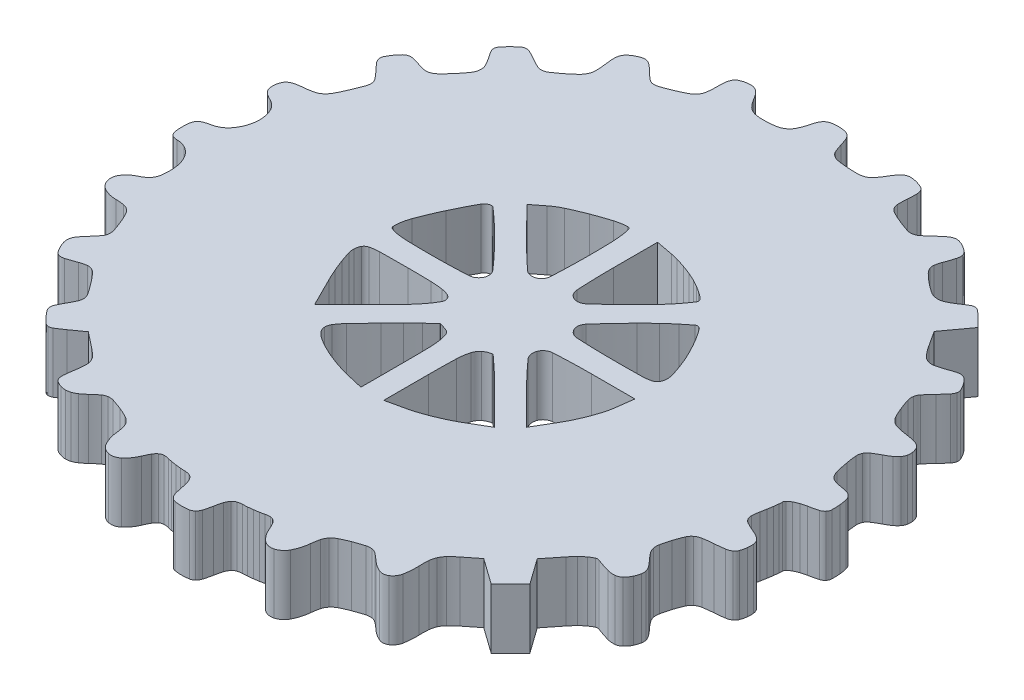
SolidWorks part; units mm, degrees
ref_plane "Front Plane" through (0, 0, 0) normal (0, 0, 1) x (1, 0, 0)
ref_plane "Top Plane" through (0, 0, 0) normal (0, 1, 0) x (1, 0, 0)
ref_plane "Right Plane" through (0, 0, 0) normal (1, 0, 0) x (0, 0, -1)
sketch "Sketch1" plane through (0, 0, 0) normal (0, 1, 0) x (1, 0, 0)
  line L204 (10740.0744, 3244.2085) -> (10740.2834, 3244.3574)
  line L205 (10740.2834, 3244.3574) -> (10740.527, 3244.1668)
  line L206 (10746.6423, 3244.2023) -> (10746.8657, 3244.3792)
  line L207 (10746.8657, 3244.3792) -> (10747.0818, 3244.2253)
  line L208 (10747.0818, 3244.2253) -> (10747.2978, 3244.0715)
  line L209 (10747.2978, 3244.0715) -> (10747.4591, 3244.2328)
  line L210 (10747.4591, 3244.2328) -> (10747.6204, 3244.3941)
  line L211 (10747.6204, 3244.3941) -> (10747.4678, 3244.6085)
  line L212 (10747.4678, 3244.6085) -> (10747.3151, 3244.8229)
  line L213 (10747.3151, 3244.8229) -> (10747.5289, 3245.0914)
  line L214 (10747.5042, 3251.1741) -> (10747.3419, 3251.4249)
  line L215 (10747.3419, 3251.4249) -> (10747.496, 3251.6365)
  line L216 (10747.496, 3251.6365) -> (10747.6501, 3251.8481)
  line L217 (10747.6501, 3251.8481) -> (10747.4943, 3252.0039)
  line L218 (10742.5971, 3249.3628) -> (10742.104, 3249.8615)
  line L219 (10742.104, 3249.8615) -> (10742.2945, 3250.0106)
  line L220 (10743.7423, 3249.6702) -> (10743.7423, 3250.405)
  line L221 (10743.7423, 3250.405) -> (10744.0245, 3250.3521)
  line L222 (10742.3156, 3247.1719) -> (10741.7813, 3246.6376)
  line L223 (10741.7813, 3246.6376) -> (10741.5426, 3247.1153)
  line L224 (10745.5314, 3246.9876) -> (10745.3248, 3246.6351)
  line L225 (10745.3248, 3246.6351) -> (10744.7969, 3247.163)
  line L226 (10745.094, 3247.9496) -> (10745.8197, 3247.9496)
  line L227 (10745.8197, 3247.9496) -> (10745.7789, 3247.6449)
  line L228 (10743.3613, 3246.5779) -> (10743.3613, 3245.8321)
  line L229 (10743.3613, 3245.8321) -> (10743.1136, 3245.8895)
  line L230 (10742.9516, 3247.272) -> (10743.0949, 3247.412)
  line L231 (10744.5341, 3246.8912) -> (10745.0551, 3246.3661)
  line L232 (10745.0551, 3246.3661) -> (10744.7226, 3246.1716)
  line L233 (10744.0661, 3245.9047) -> (10743.7423, 3245.8322)
  line L234 (10743.7423, 3245.8322) -> (10743.7423, 3246.5798)
  arc A2462 (10743.2549, 3253.2157) -> (10743.3129, 3253.3789) centre (10742.4844, 3253.5816) ccw
  arc A2463 (10743.1745, 3253.1207) -> (10743.2549, 3253.2157) centre (10743.0352, 3253.3201) ccw
  arc A2464 (10743.0513, 3253.0716) -> (10743.1745, 3253.1207) centre (10743.0082, 3253.3586) ccw
  arc A2465 (10742.8512, 3253.0562) -> (10743.0513, 3253.0716) centre (10742.8445, 3254.4507) ccw
  arc A2466 (10742.726, 3253.0669) -> (10742.8512, 3253.0562) centre (10742.8479, 3253.7578) ccw
  arc A2467 (10742.6323, 3253.101) -> (10742.726, 3253.0669) centre (10742.7756, 3253.3483) ccw
  arc A2468 (10742.555, 3253.1659) -> (10742.6323, 3253.101) centre (10742.7801, 3253.3559) ccw
  arc A2469 (10742.4801, 3253.2713) -> (10742.555, 3253.1659) centre (10743.1453, 3253.6642) ccw
  arc A2470 (10742.4801, 3253.2713) -> (10742.4087, 3253.375) centre (10741.7003, 3252.8107) ccw
  arc A2471 (10742.4087, 3253.375) -> (10742.3409, 3253.4339) centre (10742.2162, 3253.2217) ccw
  arc A2472 (10742.3409, 3253.4339) -> (10742.2652, 3253.4579) centre (10742.2502, 3253.2796) ccw
  arc A2473 (10742.2652, 3253.4579) -> (10742.171, 3253.4529) centre (10742.2362, 3253.1121) ccw
  arc A2474 (10742.171, 3253.4529) -> (10742.0772, 3253.4222) centre (10742.2438, 3253.0722) ccw
  arc A2475 (10742.0772, 3253.4222) -> (10742.0235, 3253.3729) centre (10742.1304, 3253.3104) ccw
  arc A2476 (10742.0235, 3253.3729) -> (10741.9965, 3253.29) centre (10742.2002, 3253.2696) ccw
  arc A2477 (10741.9965, 3253.29) -> (10741.9889, 3253.1414) centre (10743.5182, 3253.1371) ccw
  arc A2478 (10741.9777, 3252.9816) -> (10741.9889, 3253.1414) centre (10740.7895, 3253.1448) ccw
  arc A2479 (10741.9402, 3252.8893) -> (10741.9777, 3252.9816) centre (10741.7784, 3253.009) ccw
  arc A2480 (10741.8602, 3252.8203) -> (10741.9402, 3252.8893) centre (10741.7469, 3253.0323) ccw
  arc A2481 (10741.6923, 3252.7403) -> (10741.8602, 3252.8203) centre (10740.9214, 3254.5765) ccw
  arc A2482 (10741.5022, 3252.667) -> (10741.6923, 3252.7403) centre (10740.3306, 3255.9839) ccw
  arc A2483 (10741.4105, 3252.6574) -> (10741.5022, 3252.667) centre (10741.4366, 3252.8527) ccw
  arc A2484 (10741.3315, 3252.692) -> (10741.4105, 3252.6574) centre (10741.4312, 3252.8121) ccw
  arc A2485 (10741.2073, 3252.8053) -> (10741.3315, 3252.692) centre (10742.489, 3254.087) ccw
  arc A2486 (10741.2073, 3252.8053) -> (10741.0993, 3252.9034) centre (10740.1198, 3251.7178) ccw
  arc A2487 (10741.0993, 3252.9034) -> (10741.023, 3252.9438) centre (10740.9635, 3252.739) ccw
  arc A2488 (10741.023, 3252.9438) -> (10740.9492, 3252.9445) centre (10740.9848, 3252.8124) ccw
  arc A2489 (10740.9492, 3252.9445) -> (10740.8558, 3252.9075) centre (10741.0639, 3252.5186) ccw
  arc A2490 (10740.8558, 3252.9075) -> (10740.7745, 3252.8496) centre (10741.0402, 3252.5628) ccw
  arc A2491 (10740.7745, 3252.8496) -> (10740.7318, 3252.7833) centre (10740.8826, 3252.7329) ccw
  arc A2492 (10740.7318, 3252.7833) -> (10740.7186, 3252.69) centre (10740.9779, 3252.7011) ccw
  arc A2493 (10740.7186, 3252.69) -> (10740.7324, 3252.5378) centre (10742.343, 3252.7597) ccw
  arc A2494 (10740.7446, 3252.3753) -> (10740.7324, 3252.5378) centre (10739.4289, 3252.3582) ccw
  arc A2495 (10740.724, 3252.2714) -> (10740.7446, 3252.3753) centre (10740.4889, 3252.372) ccw
  arc A2496 (10740.6625, 3252.1822) -> (10740.724, 3252.2714) centre (10740.4725, 3252.379) ccw
  arc A2497 (10740.5318, 3252.069) -> (10740.6625, 3252.1822) centre (10739.5471, 3253.3376) ccw
  arc A2498 (10740.3771, 3251.9566) -> (10740.5318, 3252.069) centre (10738.6887, 3254.4435) ccw
  arc A2499 (10740.2935, 3251.9257) -> (10740.3771, 3251.9566) centre (10740.2726, 3252.1107) ccw
  arc A2500 (10740.2096, 3251.9392) -> (10740.2935, 3251.9257) centre (10740.2757, 3252.0826) ccw
  arc A2501 (10740.0612, 3252.0158) -> (10740.2096, 3251.9392) centre (10740.9982, 3253.6485) ccw
  arc A2502 (10740.0612, 3252.0158) -> (10739.9152, 3252.0937) centre (10738.7372, 3249.7089) ccw
  arc A2503 (10739.9152, 3252.0937) -> (10739.8415, 3252.1092) centre (10739.848, 3251.9577) ccw
  arc A2504 (10739.8415, 3252.1092) -> (10739.7773, 3252.0853) centre (10739.8462, 3251.9985) ccw
  arc A2505 (10739.7773, 3252.0853) -> (10739.6811, 3251.9996) centre (10740.4764, 3251.2043) ccw
  arc A2506 (10739.6811, 3251.9996) -> (10739.5969, 3251.9063) centre (10740.5595, 3251.1212) ccw
  arc A2507 (10739.5969, 3251.9063) -> (10739.5729, 3251.8465) centre (10739.6803, 3251.8382) ccw
  arc A2508 (10739.5729, 3251.8465) -> (10739.5871, 3251.783) centre (10739.684, 3251.838) ccw
  arc A2509 (10739.5871, 3251.783) -> (10739.656, 3251.6739) centre (10740.7691, 3252.4535) ccw
  arc A2510 (10739.748, 3251.5183) -> (10739.656, 3251.6739) centre (10738.6958, 3251.0013) ccw
  arc A2511 (10739.7662, 3251.4084) -> (10739.748, 3251.5183) centre (10739.5748, 3251.4332) ccw
  arc A2512 (10739.7218, 3251.2961) -> (10739.7662, 3251.4084) centre (10739.5221, 3251.44) ccw
  arc A2513 (10739.5848, 3251.1243) -> (10739.7218, 3251.2961) centre (10737.8807, 3252.6231) ccw
  arc A2514 (10739.4699, 3251.0052) -> (10739.5848, 3251.1243) centre (10738.2475, 3252.3005) ccw
  arc A2515 (10739.3888, 3250.9568) -> (10739.4699, 3251.0052) centre (10739.3202, 3251.1639) ccw
  arc A2516 (10739.3015, 3250.9511) -> (10739.3888, 3250.9568) centre (10739.3341, 3251.1218) ccw
  arc A2517 (10739.1694, 3250.9865) -> (10739.3015, 3250.9511) centre (10739.4769, 3251.8688) ccw
  arc A2518 (10739.1694, 3250.9865) -> (10739.0422, 3251.0231) centre (10738.776, 3249.8581) ccw
  arc A2519 (10739.0422, 3251.0231) -> (10738.9637, 3251.0223) centre (10739.0046, 3250.8588) ccw
  arc A2520 (10738.9637, 3251.0223) -> (10738.9004, 3250.9862) centre (10738.9966, 3250.8909) ccw
  arc A2521 (10738.9004, 3250.9862) -> (10738.8294, 3250.9013) centre (10739.3647, 3250.5263) ccw
  arc A2522 (10738.8294, 3250.9013) -> (10738.7704, 3250.8009) centre (10739.4297, 3250.4809) ccw
  arc A2523 (10738.7704, 3250.8009) -> (10738.7619, 3250.7322) centre (10738.8669, 3250.754) ccw
  arc A2524 (10738.7619, 3250.7322) -> (10738.7963, 3250.6607) centre (10738.9227, 3250.7656) ccw
  arc A2525 (10738.7963, 3250.6607) -> (10738.9049, 3250.5391) centre (10740.5663, 3252.1308) ccw
  arc A2526 (10739.0208, 3250.4069) -> (10738.9049, 3250.5391) centre (10737.4597, 3249.1545) ccw
  arc A2527 (10739.0544, 3250.3259) -> (10739.0208, 3250.4069) centre (10738.8987, 3250.3089) ccw
  arc A2528 (10739.0429, 3250.2317) -> (10739.0544, 3250.3259) centre (10738.8479, 3250.3033) ccw
  arc A2529 (10738.9612, 3250.0252) -> (10739.0429, 3250.2317) centre (10734.8211, 3251.7819) ccw
  arc A2530 (10738.8777, 3249.8511) -> (10738.9612, 3250.0252) centre (10737.0261, 3250.8463) ccw
  arc A2531 (10738.8043, 3249.7606) -> (10738.8777, 3249.8511) centre (10738.6034, 3249.9985) ccw
  arc A2532 (10738.7102, 3249.7122) -> (10738.8043, 3249.7606) centre (10738.6521, 3249.9408) ccw
  arc A2533 (10738.5607, 3249.687) -> (10738.7102, 3249.7122) centre (10738.4814, 3250.6127) ccw
  arc A2534 (10738.5607, 3249.687) -> (10738.4253, 3249.6676) centre (10738.6636, 3248.4846) ccw
  arc A2535 (10738.4253, 3249.6676) -> (10738.3437, 3249.6338) centre (10738.4705, 3249.4431) ccw
  arc A2536 (10738.3437, 3249.6338) -> (10738.2956, 3249.5785) centre (10738.4206, 3249.5183) ccw
  arc A2537 (10738.2956, 3249.5785) -> (10738.2697, 3249.4934) centre (10738.5567, 3249.4527) ccw
  arc A2538 (10738.2697, 3249.4934) -> (10738.2701, 3249.4097) centre (10738.5552, 3249.4529) ccw
  arc A2539 (10738.2701, 3249.4097) -> (10738.2963, 3249.3415) centre (10738.4381, 3249.4351) ccw
  arc A2540 (10738.2963, 3249.3415) -> (10738.3519, 3249.2845) centre (10738.4731, 3249.4582) ccw
  arc A2541 (10738.3519, 3249.2845) -> (10738.4412, 3249.2335) centre (10738.6761, 3249.7491) ccw
  arc A2542 (10738.6102, 3249.0567) -> (10738.4412, 3249.2335) centre (10738.3046, 3248.9338) ccw
  arc A2543 (10738.6451, 3248.7765) -> (10738.6102, 3249.0567) centre (10738.0978, 3248.8506) ccw
  arc A2544 (10738.5367, 3248.5121) -> (10738.6451, 3248.7765) centre (10738.0822, 3248.8527) ccw
  arc A2545 (10738.3253, 3248.3788) -> (10738.5367, 3248.5121) centre (10738.2567, 3248.722) ccw
  arc A2546 (10738.3253, 3248.3788) -> (10738.2081, 3248.3456) centre (10738.4781, 3247.615) ccw
  arc A2547 (10738.2081, 3248.3456) -> (10738.1445, 3248.3) centre (10738.2591, 3248.2075) ccw
  arc A2548 (10738.1445, 3248.3) -> (10738.1128, 3248.2278) centre (10738.2619, 3248.2053) ccw
  arc A2549 (10738.1128, 3248.2278) -> (10738.1035, 3248.1039) centre (10738.9338, 3248.1039) ccw
  arc A2550 (10738.1035, 3248.1039) -> (10738.1104, 3247.9899) centre (10739.0429, 3248.1039) ccw
  arc A2551 (10738.1104, 3247.9899) -> (10738.1347, 3247.9224) centre (10738.2715, 3248.0096) ccw
  arc A2552 (10738.1347, 3247.9224) -> (10738.1797, 3247.8861) centre (10738.211, 3247.9711) ccw
  arc A2553 (10738.1797, 3247.8861) -> (10738.2504, 3247.8734) centre (10738.2504, 3248.0777) ccw
  arc A2554 (10738.4031, 3247.8361) -> (10738.2504, 3247.8734) centre (10738.2504, 3247.5425) ccw
  arc A2555 (10738.5278, 3247.7316) -> (10738.4031, 3247.8361) centre (10738.2294, 3247.5021) ccw
  arc A2556 (10738.6091, 3247.5702) -> (10738.5278, 3247.7316) centre (10738.147, 3247.4387) ccw
  arc A2557 (10738.6369, 3247.3711) -> (10738.6091, 3247.5702) centre (10737.9092, 3247.3711) ccw
  arc A2558 (10738.6277, 3247.2357) -> (10738.6369, 3247.3711) centre (10737.6336, 3247.3711) ccw
  arc A2559 (10738.5977, 3247.1444) -> (10738.6277, 3247.2357) centre (10738.3642, 3247.2715) ccw
  arc A2560 (10738.5404, 3247.0776) -> (10738.5977, 3247.1444) centre (10738.4131, 3247.2449) ccw
  arc A2561 (10738.4464, 3247.0214) -> (10738.5404, 3247.0776) centre (10738.2422, 3247.4695) ccw
  arc A2562 (10738.4464, 3247.0214) -> (10738.2839, 3246.8828) centre (10738.6074, 3246.668) ccw
  arc A2563 (10738.2839, 3246.8828) -> (10738.2569, 3246.7049) centre (10738.4615, 3246.7649) ccw
  arc A2564 (10738.2569, 3246.7049) -> (10738.3772, 3246.5572) centre (10738.4927, 3246.774) ccw
  arc A2565 (10738.3772, 3246.5572) -> (10738.5988, 3246.5018) centre (10738.5988, 3246.9732) ccw
  arc A2566 (10738.739, 3246.4903) -> (10738.5988, 3246.5018) centre (10738.5988, 3245.6428) ccw
  arc A2567 (10738.8258, 3246.4522) -> (10738.739, 3246.4903) centre (10738.7077, 3246.301) ccw
  arc A2568 (10738.8919, 3246.3732) -> (10738.8258, 3246.4522) centre (10738.6748, 3246.2589) ccw
  arc A2569 (10738.9648, 3246.2161) -> (10738.8919, 3246.3732) centre (10737.3608, 3245.5668) ccw
  arc A2570 (10739.0302, 3246.0376) -> (10738.9648, 3246.2161) centre (10736.329, 3245.1492) ccw
  arc A2571 (10739.0393, 3245.9438) -> (10739.0302, 3246.0376) centre (10738.8261, 3245.9705) ccw
  arc A2572 (10739.0064, 3245.862) -> (10739.0393, 3245.9438) centre (10738.8676, 3245.9653) ccw
  arc A2573 (10738.9053, 3245.7398) -> (10739.0064, 3245.862) centre (10737.7813, 3246.7735) ccw
  arc A2574 (10738.9053, 3245.7398) -> (10738.8178, 3245.6335) centre (10739.828, 3244.8912) ccw
  arc A2575 (10738.8178, 3245.6335) -> (10738.7793, 3245.553) centre (10739.0107, 3245.4917) ccw
  arc A2576 (10738.7793, 3245.553) -> (10738.7773, 3245.4744) centre (10738.9432, 3245.5096) ccw
  arc A2577 (10738.7773, 3245.4744) -> (10738.8094, 3245.3779) centre (10739.2221, 3245.5688) ccw
  arc A2578 (10738.8094, 3245.3779) -> (10738.8751, 3245.2613) centre (10739.5736, 3245.7315) ccw
  arc A2579 (10738.8751, 3245.2613) -> (10738.9372, 3245.2177) centre (10738.9628, 3245.3203) ccw
  arc A2580 (10738.9372, 3245.2177) -> (10739.0245, 3245.2198) centre (10738.977, 3245.3774) ccw
  arc A2581 (10739.0245, 3245.2198) -> (10739.2015, 3245.28) centre (10738.2661, 3247.7404) ccw
  arc A2582 (10739.3152, 3245.3089) -> (10739.2015, 3245.28) centre (10739.3843, 3244.7992) ccw
  arc A2583 (10739.3975, 3245.2954) -> (10739.3152, 3245.3089) centre (10739.3343, 3245.168) ccw
  arc A2584 (10739.479, 3245.2327) -> (10739.3975, 3245.2954) centre (10739.2801, 3245.0587) ccw
  arc A2585 (10739.603, 3245.081) -> (10739.479, 3245.2327) centre (10737.2943, 3243.32) ccw
  arc A2586 (10739.7276, 3244.9081) -> (10739.603, 3245.081) centre (10736.4902, 3242.7068) ccw
  arc A2587 (10739.7647, 3244.8166) -> (10739.7276, 3244.9081) centre (10739.5333, 3244.776) ccw
  arc A2588 (10739.7551, 3244.7302) -> (10739.7647, 3244.8166) centre (10739.612, 3244.7898) ccw
  arc A2589 (10739.6884, 3244.5948) -> (10739.7551, 3244.7302) centre (10738.65, 3245.1908) ccw
  arc A2590 (10739.6884, 3244.5948) -> (10739.6199, 3244.4632) centre (10741.2543, 3243.6962) ccw
  arc A2591 (10739.6199, 3244.4632) -> (10739.6062, 3244.3891) centre (10739.7546, 3244.3999) ccw
  arc A2592 (10739.6062, 3244.3891) -> (10739.6313, 3244.3217) centre (10739.7343, 3244.3984) ccw
  arc A2593 (10739.6313, 3244.3217) -> (10739.7157, 3244.2205) centre (10740.5942, 3245.039) ccw
  arc A2594 (10739.7157, 3244.2205) -> (10739.8153, 3244.1222) centre (10740.9298, 3245.3516) ccw
  arc A2595 (10739.8153, 3244.1222) -> (10739.8729, 3244.0989) centre (10739.8759, 3244.189) ccw
  arc A2596 (10739.8729, 3244.0989) -> (10739.9368, 3244.1162) centre (10739.8767, 3244.2114) ccw
  arc A2597 (10739.9368, 3244.1162) -> (10740.0744, 3244.2085) centre (10738.3427, 3246.6405) ccw
  arc A2598 (10740.663, 3244.0489) -> (10740.527, 3244.1668) centre (10739.4205, 3242.7529) ccw
  arc A2599 (10740.7235, 3243.9598) -> (10740.663, 3244.0489) centre (10740.4837, 3243.8618) ccw
  arc A2600 (10740.7415, 3243.8556) -> (10740.7235, 3243.9598) centre (10740.4963, 3243.867) ccw
  arc A2601 (10740.7239, 3243.6847) -> (10740.7415, 3243.8556) centre (10739.2106, 3243.9267) ccw
  arc A2602 (10740.7239, 3243.6847) -> (10740.7036, 3243.52) centre (10743.0174, 3243.318) ccw
  arc A2603 (10740.7036, 3243.52) -> (10740.7143, 3243.4345) centre (10740.9074, 3243.5022) ccw
  arc A2604 (10740.7143, 3243.4345) -> (10740.7569, 3243.381) centre (10740.8124, 3243.4689) ccw
  arc A2605 (10740.7569, 3243.381) -> (10740.8447, 3243.3402) centre (10740.9593, 3243.7014) ccw
  arc A2606 (10740.8447, 3243.3402) -> (10740.9319, 3243.326) centre (10740.9364, 3243.6293) ccw
  arc A2607 (10740.9319, 3243.326) -> (10741.015, 3243.3389) centre (10740.9356, 3243.5764) ccw
  arc A2608 (10741.015, 3243.3389) -> (10741.0997, 3243.3814) centre (10740.9093, 3243.6552) ccw
  arc A2609 (10741.0997, 3243.3814) -> (10741.1922, 3243.4563) centre (10740.6355, 3244.0489) ccw
  arc A2610 (10741.3077, 3243.5531) -> (10741.1922, 3243.4563) centre (10742.0958, 3242.4945) ccw
  arc A2611 (10741.3881, 3243.5849) -> (10741.3077, 3243.5531) centre (10741.4072, 3243.4195) ccw
  arc A2612 (10741.4819, 3243.5755) -> (10741.3881, 3243.5849) centre (10741.4135, 3243.3649) ccw
  arc A2613 (10741.662, 3243.5106) -> (10741.4819, 3243.5755) centre (10740.5565, 3240.7262) ccw
  arc A2614 (10741.8172, 3243.4389) -> (10741.662, 3243.5106) centre (10741.088, 3242.065) ccw
  arc A2615 (10741.9031, 3243.3698) -> (10741.8172, 3243.4389) centre (10741.68, 3243.1805) ccw
  arc A2616 (10741.9509, 3243.2793) -> (10741.9031, 3243.3698) centre (10741.7224, 3243.2164) ccw
  arc A2617 (10741.9768, 3243.1397) -> (10741.9509, 3243.2793) centre (10741.1463, 3243.0577) ccw
  arc A2618 (10741.9768, 3243.1397) -> (10742.0526, 3242.8886) centre (10742.65, 3243.2061) ccw
  arc A2619 (10742.0526, 3242.8886) -> (10742.208, 3242.7672) centre (10742.2668, 3243.0025) ccw
  arc A2620 (10742.208, 3242.7672) -> (10742.3851, 3242.809) centre (10742.2561, 3242.9595) ccw
  arc A2621 (10742.3851, 3242.809) -> (10742.5255, 3243.0025) centre (10742.0508, 3243.1991) ccw
  arc A2622 (10742.5817, 3243.1187) -> (10742.5255, 3243.0025) centre (10743.5528, 3242.5769) ccw
  arc A2623 (10742.6355, 3243.18) -> (10742.5817, 3243.1187) centre (10742.752, 3243.0237) ccw
  arc A2624 (10742.6987, 3243.2028) -> (10742.6355, 3243.18) centre (10742.7048, 3243.087) ccw
  arc A2625 (10742.7824, 3243.194) -> (10742.6987, 3243.2028) centre (10742.7127, 3242.9345) ccw
  arc A2626 (10742.7824, 3243.194) -> (10742.8554, 3243.1775) centre (10743.027, 3244.1054) ccw
  arc A2627 (10742.8554, 3243.1775) -> (10742.9431, 3243.1634) centre (10743.1947, 3245.0115) ccw
  arc A2628 (10742.9431, 3243.1634) -> (10743.0312, 3243.1536) centre (10743.1938, 3245.0051) ccw
  arc A2629 (10743.0312, 3243.1536) -> (10743.1051, 3243.1501) centre (10743.111, 3244.0619) ccw
  arc A2630 (10743.1866, 3243.135) -> (10743.1051, 3243.1501) centre (10743.1036, 3242.9145) ccw
  arc A2631 (10743.2443, 3243.093) -> (10743.1866, 3243.135) centre (10743.1394, 3243.0096) ccw
  arc A2632 (10743.2856, 3243.0145) -> (10743.2443, 3243.093) centre (10743.058, 3242.9448) ccw
  arc A2633 (10743.3181, 3242.8823) -> (10743.2856, 3243.0145) centre (10742.1209, 3242.6577) ccw
  arc A2634 (10743.3181, 3242.8823) -> (10743.3536, 3242.736) centre (10744.7277, 3243.1468) ccw
  arc A2635 (10743.3536, 3242.736) -> (10743.3975, 3242.6625) centre (10743.521, 3242.7861) ccw
  arc A2636 (10743.3975, 3242.6625) -> (10743.466, 3242.6265) centre (10743.4897, 3242.7548) ccw
  arc A2637 (10743.466, 3242.6265) -> (10743.5848, 3242.6156) centre (10743.5848, 3243.2707) ccw
  arc A2638 (10743.5848, 3242.6156) -> (10743.7036, 3242.6265) centre (10743.5848, 3243.2707) ccw
  arc A2639 (10743.7036, 3242.6265) -> (10743.7722, 3242.6625) centre (10743.68, 3242.7548) ccw
  arc A2640 (10743.7722, 3242.6625) -> (10743.816, 3242.736) centre (10743.6487, 3242.7861) ccw
  arc A2641 (10743.816, 3242.736) -> (10743.8515, 3242.8823) centre (10742.442, 3243.1468) ccw
  arc A2642 (10743.8844, 3243.0161) -> (10743.8515, 3242.8823) centre (10745.0748, 3242.6528) ccw
  arc A2643 (10743.926, 3243.0941) -> (10743.8844, 3243.0161) centre (10744.104, 3242.9491) ccw
  arc A2644 (10743.9848, 3243.1354) -> (10743.926, 3243.0941) centre (10744.0285, 3243.0106) ccw
  arc A2645 (10744.0696, 3243.1501) -> (10743.9848, 3243.1354) centre (10744.0712, 3242.8886) ccw
  arc A2646 (10744.0696, 3243.1501) -> (10744.1455, 3243.1536) centre (10744.0636, 3244.1077) ccw
  arc A2647 (10744.1455, 3243.1536) -> (10744.2352, 3243.1634) centre (10743.9838, 3245.0389) ccw
  arc A2648 (10744.2352, 3243.1634) -> (10744.324, 3243.1775) centre (10743.9846, 3245.0323) ccw
  arc A2649 (10744.324, 3243.1775) -> (10744.3974, 3243.194) centre (10744.1576, 3244.0872) ccw
  arc A2650 (10744.481, 3243.2028) -> (10744.3974, 3243.194) centre (10744.467, 3242.9345) ccw
  arc A2651 (10744.5443, 3243.18) -> (10744.481, 3243.2028) centre (10744.475, 3243.087) ccw
  arc A2652 (10744.598, 3243.1187) -> (10744.5443, 3243.18) centre (10744.4277, 3243.0237) ccw
  arc A2653 (10744.6542, 3243.0025) -> (10744.598, 3243.1187) centre (10743.6269, 3242.5769) ccw
  arc A2654 (10744.6542, 3243.0025) -> (10744.7953, 3242.8077) centre (10745.1328, 3243.2007) ccw
  arc A2655 (10744.7953, 3242.8077) -> (10744.9725, 3242.767) centre (10744.9227, 3242.956) ccw
  arc A2656 (10744.9725, 3242.767) -> (10745.1277, 3242.8914) centre (10744.9101, 3243.0038) ccw
  arc A2657 (10745.1277, 3242.8914) -> (10745.2029, 3243.147) centre (10744.503, 3243.2141) ccw
  arc A2658 (10745.2284, 3243.2922) -> (10745.2029, 3243.147) centre (10746.1392, 3243.0572) ccw
  arc A2659 (10745.2751, 3243.3828) -> (10745.2284, 3243.2922) centre (10745.4512, 3243.2347) ccw
  arc A2660 (10745.3598, 3243.4502) -> (10745.2751, 3243.3828) centre (10745.484, 3243.2071) ccw
  arc A2661 (10745.5161, 3243.5195) -> (10745.3598, 3243.4502) centre (10746.0659, 3242.0688) ccw
  arc A2662 (10745.6946, 3243.58) -> (10745.5161, 3243.5195) centre (10746.462, 3241.0234) ccw
  arc A2663 (10745.7902, 3243.5869) -> (10745.6946, 3243.58) centre (10745.758, 3243.3688) ccw
  arc A2664 (10745.8735, 3243.5519) -> (10745.7902, 3243.5869) centre (10745.7637, 3243.4072) ccw
  arc A2665 (10745.9958, 3243.4485) -> (10745.8735, 3243.5519) centre (10744.9491, 3242.3343) ccw
  arc A2666 (10745.9958, 3243.4485) -> (10746.1766, 3243.3303) centre (10746.4211, 3243.9012) ccw
  arc A2667 (10746.1766, 3243.3303) -> (10746.3217, 3243.3426) centre (10746.2376, 3243.4727) ccw
  arc A2668 (10746.3217, 3243.3426) -> (10746.4141, 3243.4783) centre (10746.2071, 3243.5199) ccw
  arc A2669 (10746.4141, 3243.4783) -> (10746.4331, 3243.7311) centre (10745.4043, 3243.6813) ccw
  arc A2670 (10746.4357, 3243.8918) -> (10746.4331, 3243.7311) centre (10747.6804, 3243.7916) ccw
  arc A2671 (10746.464, 3244.0031) -> (10746.4357, 3243.8918) centre (10746.7765, 3243.8643) ccw
  arc A2672 (10746.5271, 3244.0973) -> (10746.464, 3244.0031) centre (10746.7662, 3243.8689) ccw
  arc A2673 (10746.6423, 3244.2023) -> (10746.5271, 3244.0973) centre (10747.3414, 3243.3194) ccw
  arc A2674 (10747.6192, 3245.1927) -> (10747.5289, 3245.0914) centre (10748.4851, 3244.3302) ccw
  arc A2675 (10747.7104, 3245.2707) -> (10747.6192, 3245.1927) centre (10748.1536, 3244.6603) ccw
  arc A2676 (10747.7913, 3245.3188) -> (10747.7104, 3245.2707) centre (10748.0128, 3244.8543) ccw
  arc A2677 (10747.8451, 3245.321) -> (10747.7913, 3245.3188) centre (10747.8207, 3245.257) ccw
  arc A2678 (10747.8451, 3245.321) -> (10748.0696, 3245.2458) centre (10748.871, 3248.0126) ccw
  arc A2679 (10748.0696, 3245.2458) -> (10748.2051, 3245.2334) centre (10748.1695, 3245.5906) ccw
  arc A2680 (10748.2051, 3245.2334) -> (10748.297, 3245.2749) centre (10748.1894, 3245.3905) ccw
  arc A2681 (10748.297, 3245.2749) -> (10748.3682, 3245.3731) centre (10748.0832, 3245.5048) ccw
  arc A2682 (10748.3682, 3245.3731) -> (10748.4021, 3245.4732) centre (10747.9146, 3245.5827) ccw
  arc A2683 (10748.4021, 3245.4732) -> (10748.4005, 3245.5524) centre (10748.2402, 3245.5096) ccw
  arc A2684 (10748.4005, 3245.5524) -> (10748.3612, 3245.633) centre (10748.1745, 3245.492) ccw
  arc A2685 (10748.3612, 3245.633) -> (10748.2696, 3245.742) centre (10747.2786, 3244.8158) ccw
  arc A2686 (10748.1713, 3245.8604) -> (10748.2696, 3245.742) centre (10749.2215, 3246.6316) ccw
  arc A2687 (10748.1324, 3245.9487) -> (10748.1713, 3245.8604) centre (10748.3508, 3245.9922) ccw
  arc A2688 (10748.1329, 3246.049) -> (10748.1324, 3245.9487) centre (10748.3787, 3245.9978) ccw
  arc A2689 (10748.1754, 3246.2144) -> (10748.1329, 3246.049) centre (10749.9483, 3245.6703) ccw
  arc A2690 (10748.2351, 3246.3757) -> (10748.1754, 3246.2144) centre (10749.6251, 3245.7695) ccw
  arc A2691 (10748.2967, 3246.454) -> (10748.2351, 3246.3757) centre (10748.4163, 3246.2967) ccw
  arc A2692 (10748.3905, 3246.4948) -> (10748.2967, 3246.454) centre (10748.4267, 3246.283) ccw
  arc A2693 (10748.5735, 3246.5171) -> (10748.3905, 3246.4948) centre (10748.7137, 3244.6029) ccw
  arc A2694 (10748.5735, 3246.5171) -> (10748.7486, 3246.5367) centre (10748.4067, 3248.7951) ccw
  arc A2695 (10748.7486, 3246.5367) -> (10748.8359, 3246.5703) centre (10748.7161, 3246.7516) ccw
  arc A2696 (10748.8359, 3246.5703) -> (10748.8834, 3246.6306) centre (10748.7686, 3246.6721) ccw
  arc A2697 (10748.8834, 3246.6306) -> (10748.9088, 3246.7386) centre (10748.4313, 3246.794) ccw
  arc A2698 (10748.9088, 3246.7386) -> (10748.909, 3246.844) centre (10748.4501, 3246.7918) ccw
  arc A2699 (10748.909, 3246.844) -> (10748.8803, 3246.9177) centre (10748.7548, 3246.8264) ccw
  arc A2700 (10748.8803, 3246.9177) -> (10748.8145, 3246.9766) centre (10748.7105, 3246.7942) ccw
  arc A2701 (10748.8145, 3246.9766) -> (10748.6922, 3247.0365) centre (10748.2767, 3246.0335) ccw
  arc A2702 (10748.5599, 3247.1) -> (10748.6922, 3247.0365) centre (10749.2051, 3248.2747) ccw
  arc A2703 (10748.5006, 3247.1572) -> (10748.5599, 3247.1) centre (10748.6357, 3247.238) ccw
  arc A2704 (10748.4817, 3247.2331) -> (10748.5006, 3247.1572) centre (10748.6162, 3247.2263) ccw
  arc A2705 (10748.4977, 3247.3617) -> (10748.4817, 3247.2331) centre (10749.3629, 3247.1887) ccw
  arc A2706 (10748.4977, 3247.3617) -> (10748.515, 3247.4557) centre (10745.4331, 3247.9747) ccw
  arc A2707 (10748.515, 3247.4557) -> (10748.5296, 3247.5511) centre (10745.3021, 3247.9967) ccw
  arc A2708 (10748.5296, 3247.5511) -> (10748.54, 3247.6354) centre (10745.6655, 3247.9466) ccw
  arc A2709 (10748.54, 3247.6354) -> (10748.5429, 3247.689) centre (10748.0444, 3247.689) ccw
  arc A2710 (10748.5616, 3247.7315) -> (10748.5429, 3247.689) centre (10748.6005, 3247.689) ccw
  arc A2711 (10748.6224, 3247.7755) -> (10748.5616, 3247.7315) centre (10748.7831, 3247.4893) ccw
  arc A2712 (10748.71, 3247.8143) -> (10748.6224, 3247.7755) centre (10748.8694, 3247.3358) ccw
  arc A2713 (10748.8137, 3247.8411) -> (10748.71, 3247.8143) centre (10748.9589, 3247.067) ccw
  arc A2714 (10748.8137, 3247.8411) -> (10748.9715, 3247.8781) centre (10748.4788, 3249.6262) ccw
  arc A2715 (10748.9715, 3247.8781) -> (10749.0388, 3247.9211) centre (10748.934, 3248.0108) ccw
  arc A2716 (10749.0388, 3247.9211) -> (10749.0659, 3247.9911) centre (10748.953, 3247.9946) ccw
  arc A2717 (10749.0659, 3247.9911) -> (10749.0614, 3248.1303) centre (10747.9805, 3248.0252) ccw
  arc A2718 (10749.0614, 3248.1303) -> (10749.0408, 3248.2517) centre (10748.1986, 3248.0464) ccw
  arc A2719 (10749.0408, 3248.2517) -> (10749.0042, 3248.3255) centre (10748.858, 3248.2072) ccw
  arc A2720 (10749.0042, 3248.3255) -> (10748.9436, 3248.3696) centre (10748.8912, 3248.2341) ccw
  arc A2721 (10748.9436, 3248.3696) -> (10748.8477, 3248.3942) centre (10748.7918, 3247.9767) ccw
  arc A2722 (10748.6932, 3248.4281) -> (10748.8477, 3248.3942) centre (10748.9746, 3249.3427) ccw
  arc A2723 (10748.6099, 3248.484) -> (10748.6932, 3248.4281) centre (10748.7444, 3248.5945) ccw
  arc A2724 (10748.558, 3248.5864) -> (10748.6099, 3248.484) centre (10748.8135, 3248.6513) ccw
  arc A2725 (10748.5112, 3248.8035) -> (10748.558, 3248.5864) centre (10751.4942, 3249.3334) ccw
  arc A2726 (10748.4895, 3248.9715) -> (10748.5112, 3248.8035) centre (10750.2788, 3249.1175) ccw
  arc A2727 (10748.5053, 3249.0611) -> (10748.4895, 3248.9715) centre (10748.6683, 3248.9861) ccw
  arc A2728 (10748.5624, 3249.1282) -> (10748.5053, 3249.0611) centre (10748.6531, 3248.9931) ccw
  arc A2729 (10748.6972, 3249.2079) -> (10748.5624, 3249.1282) centre (10749.3275, 3247.989) ccw
  arc A2730 (10748.6972, 3249.2079) -> (10748.8074, 3249.2745) centre (10748.2494, 3250.0738) ccw
  arc A2731 (10748.8074, 3249.2745) -> (10748.8747, 3249.3402) centre (10748.6426, 3249.5106) ccw
  arc A2732 (10748.8747, 3249.3402) -> (10748.9068, 3249.4122) centre (10748.7249, 3249.4502) ccw
  arc A2733 (10748.9068, 3249.4122) -> (10748.9095, 3249.4971) centre (10748.666, 3249.4624) ccw
  arc A2734 (10748.9095, 3249.4971) -> (10748.8822, 3249.5807) centre (10748.659, 3249.4614) ccw
  arc A2735 (10748.8822, 3249.5807) -> (10748.8298, 3249.6375) centre (10748.7466, 3249.5083) ccw
  arc A2736 (10748.8298, 3249.6375) -> (10748.7402, 3249.6754) centre (10748.6762, 3249.399) ccw
  arc A2737 (10748.7402, 3249.6754) -> (10748.5911, 3249.7022) centre (10748.3945, 3248.1817) ccw
  arc A2738 (10748.4262, 3249.7344) -> (10748.5911, 3249.7022) centre (10748.7592, 3251.0029) ccw
  arc A2739 (10748.3275, 3249.784) -> (10748.4262, 3249.7344) centre (10748.4937, 3249.9916) ccw
  arc A2740 (10748.2555, 3249.8706) -> (10748.3275, 3249.784) centre (10748.5032, 3250.0035) ccw
  arc A2741 (10748.1811, 3250.0306) -> (10748.2555, 3249.8706) centre (10749.6181, 3250.6014) ccw
  arc A2742 (10748.1152, 3250.2148) -> (10748.1811, 3250.0306) centre (10750.8126, 3251.076) ccw
  arc A2743 (10748.1084, 3250.3097) -> (10748.1152, 3250.2148) centre (10748.3072, 3250.2761) ccw
  arc A2744 (10748.1464, 3250.394) -> (10748.1084, 3250.3097) centre (10748.2884, 3250.2793) ccw
  arc A2745 (10748.2654, 3250.5292) -> (10748.1464, 3250.394) centre (10749.8022, 3249.0568) ccw
  arc A2746 (10748.2654, 3250.5292) -> (10748.3805, 3250.6576) centre (10746.3642, 3252.3506) ccw
  arc A2747 (10748.3805, 3250.6576) -> (10748.4169, 3250.731) centre (10748.248, 3250.7688) ccw
  arc A2748 (10748.4169, 3250.731) -> (10748.4089, 3250.8009) centre (10748.3123, 3250.7544) ccw
  arc A2749 (10748.4089, 3250.8009) -> (10748.3492, 3250.9029) centre (10747.7537, 3250.4858) ccw
  arc A2750 (10748.3492, 3250.9029) -> (10748.2803, 3250.986) centre (10747.8039, 3250.521) ccw
  arc A2751 (10748.2803, 3250.986) -> (10748.2187, 3251.0232) centre (10748.1779, 3250.8861) ccw
  arc A2752 (10748.2187, 3251.0232) -> (10748.1462, 3251.0261) centre (10748.1768, 3250.8822) ccw
  arc A2753 (10748.1462, 3251.0261) -> (10748.0402, 3250.9948) centre (10748.2958, 3250.3227) ccw
  arc A2754 (10747.8464, 3250.9354) -> (10748.0402, 3250.9948) centre (10747.4898, 3252.4425) ccw
  arc A2755 (10747.7267, 3250.9408) -> (10747.8464, 3250.9354) centre (10747.7961, 3251.1482) ccw
  arc A2756 (10747.6268, 3251.0086) -> (10747.7267, 3250.9408) centre (10747.7975, 3251.1525) ccw
  arc A2757 (10747.5042, 3251.1741) -> (10747.6268, 3251.0086) centre (10748.8772, 3252.0629) ccw
  arc A2758 (10747.4943, 3252.0039) -> (10747.3966, 3252.0928) centre (10746.5013, 3251.0108) ccw
  arc A2759 (10747.3966, 3252.0928) -> (10747.3354, 3252.1182) centre (10747.3246, 3252.0058) ccw
  arc A2760 (10747.3354, 3252.1182) -> (10747.2711, 3252.1046) centre (10747.3249, 3252.0089) ccw
  arc A2761 (10747.2711, 3252.1046) -> (10747.1617, 3252.0359) centre (10747.9087, 3250.9694) ccw
  arc A2762 (10747.0003, 3251.9427) -> (10747.1617, 3252.0359) centre (10746.5507, 3252.9083) ccw
  arc A2763 (10746.8784, 3251.9232) -> (10747.0003, 3251.9427) centre (10746.9052, 3252.1469) ccw
  arc A2764 (10746.7527, 3251.9698) -> (10746.8784, 3251.9232) centre (10746.9125, 3252.2085) ccw
  arc A2765 (10746.5709, 3252.1065) -> (10746.7527, 3251.9698) centre (10747.9098, 3253.6977) ccw
  arc A2766 (10746.4473, 3252.2199) -> (10746.5709, 3252.1065) centre (10747.8244, 3253.5962) ccw
  arc A2767 (10746.3938, 3252.3004) -> (10746.4473, 3252.2199) centre (10746.6211, 3252.3936) ccw
  arc A2768 (10746.3838, 3252.3822) -> (10746.3938, 3252.3004) centre (10746.5375, 3252.3593) ccw
  arc A2769 (10746.4126, 3252.4924) -> (10746.3838, 3252.3822) centre (10746.9079, 3252.3041) ccw
  arc A2770 (10746.4126, 3252.4924) -> (10746.4718, 3252.6692) centre (10744.2664, 3253.3084) ccw
  arc A2771 (10746.4718, 3252.6692) -> (10746.4753, 3252.765) centre (10746.2819, 3252.7243) ccw
  arc A2772 (10746.4753, 3252.765) -> (10746.4328, 3252.835) centre (10746.3546, 3252.7396) ccw
  arc A2773 (10746.4328, 3252.835) -> (10746.3253, 3252.9068) centre (10746.0116, 3252.3206) ccw
  arc A2774 (10746.3253, 3252.9068) -> (10746.233, 3252.9425) centre (10746.1344, 3252.55) ccw
  arc A2775 (10746.233, 3252.9425) -> (10746.1574, 3252.9411) centre (10746.1977, 3252.8021) ccw
  arc A2776 (10746.1574, 3252.9411) -> (10746.0773, 3252.9001) centre (10746.2232, 3252.7141) ccw
  arc A2777 (10746.0773, 3252.9001) -> (10745.9634, 3252.802) centre (10747.0901, 3251.6086) ccw
  arc A2778 (10745.8325, 3252.6891) -> (10745.9634, 3252.802) centre (10744.649, 3254.194) ccw
  arc A2779 (10745.7495, 3252.6534) -> (10745.8325, 3252.6891) centre (10745.7237, 3252.8275) ccw
  arc A2780 (10745.6551, 3252.6615) -> (10745.7495, 3252.6534) centre (10745.7194, 3252.8564) ccw
  arc A2781 (10745.4709, 3252.7291) -> (10745.6551, 3252.6615) centre (10746.5858, 3255.4843) ccw
  arc A2782 (10745.3014, 3252.8062) -> (10745.4709, 3252.7291) centre (10746.2876, 3254.7475) ccw
  arc A2783 (10745.2283, 3252.8701) -> (10745.3014, 3252.8062) centre (10745.3908, 3252.9821) ccw
  arc A2784 (10745.1995, 3252.957) -> (10745.2283, 3252.8701) centre (10745.3632, 3252.9631) ccw
  arc A2785 (10745.2034, 3253.117) -> (10745.1995, 3252.957) centre (10746.5002, 3253.0053) ccw
  arc A2786 (10745.2034, 3253.117) -> (10745.2092, 3253.2688) centre (10743.6135, 3253.254) ccw
  arc A2787 (10745.2092, 3253.2688) -> (10745.1884, 3253.3497) centre (10745.0356, 3253.2672) ccw
  arc A2788 (10745.1884, 3253.3497) -> (10745.1351, 3253.4007) centre (10745.0826, 3253.2925) ccw
  arc A2789 (10745.1351, 3253.4007) -> (10745.0287, 3253.4403) centre (10744.8743, 3252.8628) ccw
  arc A2790 (10745.0287, 3253.4403) -> (10744.9195, 3253.458) centre (10744.8865, 3252.9085) ccw
  arc A2791 (10744.9195, 3253.458) -> (10744.843, 3253.4419) centre (10744.9106, 3253.3108) ccw
  arc A2792 (10744.843, 3253.4419) -> (10744.7769, 3253.3863) centre (10744.9328, 3253.268) ccw
  arc A2793 (10744.7769, 3253.3863) -> (10744.6989, 3253.2701) centre (10745.7409, 3252.6546) ccw
  arc A2794 (10744.6142, 3253.1483) -> (10744.6989, 3253.2701) centre (10743.8306, 3253.783) ccw
  arc A2795 (10744.5363, 3253.0883) -> (10744.6142, 3253.1483) centre (10744.4498, 3253.2815) ccw
  arc A2796 (10744.4327, 3253.0651) -> (10744.5363, 3253.0883) centre (10744.4276, 3253.3309) ccw
  arc A2797 (10744.2524, 3253.07) -> (10744.4327, 3253.0651) centre (10744.3955, 3255.0193) ccw
  arc A2798 (10744.0715, 3253.0915) -> (10744.2524, 3253.07) centre (10744.4002, 3255.0843) ccw
  arc A2799 (10743.9776, 3253.1299) -> (10744.0715, 3253.0915) centre (10744.1086, 3253.3163) ccw
  arc A2800 (10743.918, 3253.2018) -> (10743.9776, 3253.1299) centre (10744.0797, 3253.2751) ccw
  arc A2801 (10743.867, 3253.3408) -> (10743.918, 3253.2018) centre (10744.8298, 3253.6153) ccw
  arc A2802 (10743.867, 3253.3408) -> (10743.8209, 3253.4703) centre (10742.8456, 3253.0495) ccw
  arc A2803 (10743.8209, 3253.4703) -> (10743.7687, 3253.5413) centre (10743.64, 3253.3923) ccw
  arc A2804 (10743.7687, 3253.5413) -> (10743.6952, 3253.5772) centre (10743.6642, 3253.4203) ccw
  arc A2805 (10743.6952, 3253.5772) -> (10743.5803, 3253.5884) centre (10743.5803, 3252.9958) ccw
  arc A2806 (10743.5803, 3253.5884) -> (10743.4688, 3253.5785) centre (10743.5803, 3252.9593) ccw
  arc A2807 (10743.4688, 3253.5785) -> (10743.3972, 3253.5464) centre (10743.4977, 3253.4182) ccw
  arc A2808 (10743.3972, 3253.5464) -> (10743.349, 3253.4846) centre (10743.4975, 3253.4185) ccw
  arc A2809 (10743.349, 3253.4846) -> (10743.3129, 3253.3789) centre (10743.9204, 3253.2302) ccw
  arc A2810 (10743.3444, 3249.0091) -> (10743.3613, 3249.626) centre (10732.098, 3249.626) ccw
  arc A2811 (10743.2416, 3248.8731) -> (10743.3444, 3249.0091) centre (10743.1919, 3249.0174) ccw
  arc A2812 (10743.0669, 3248.9095) -> (10743.2416, 3248.8731) centre (10743.1849, 3249.0378) ccw
  arc A2813 (10742.5971, 3249.3628) -> (10743.0669, 3248.9095) centre (10752.3791, 3259.0345) ccw
  arc A2814 (10742.4736, 3250.1204) -> (10742.2945, 3250.0106) centre (10742.8638, 3249.2833) ccw
  arc A2815 (10742.7655, 3250.2442) -> (10742.4736, 3250.1204) centre (10744.3771, 3246.0366) ccw
  arc A2816 (10743.0645, 3250.3469) -> (10742.7655, 3250.2442) centre (10744.3857, 3246.0144) ccw
  arc A2817 (10743.266, 3250.3827) -> (10743.0645, 3250.3469) centre (10743.3135, 3249.5304) ccw
  arc A2818 (10743.3122, 3250.3501) -> (10743.266, 3250.3827) centre (10743.2685, 3250.3373) ccw
  arc A2819 (10743.34, 3250.2165) -> (10743.3122, 3250.3501) centre (10742.4897, 3250.1094) ccw
  arc A2820 (10743.3567, 3249.9935) -> (10743.34, 3250.2165) centre (10741.1307, 3249.9384) ccw
  arc A2821 (10743.3613, 3249.626) -> (10743.3567, 3249.9935) centre (10728.5128, 3249.6261) ccw
  arc A2822 (10744.7035, 3250.0924) -> (10744.5908, 3250.1542) centre (10743.6145, 3248.2405) ccw
  arc A2823 (10744.807, 3250.0266) -> (10744.7035, 3250.0924) centre (10743.7975, 3248.5517) ccw
  arc A2824 (10744.8905, 3249.9653) -> (10744.807, 3250.0266) centre (10743.9191, 3248.7294) ccw
  arc A2825 (10744.928, 3249.9234) -> (10744.8905, 3249.9653) centre (10744.791, 3249.8387) ccw
  arc A2826 (10744.9273, 3249.8658) -> (10744.928, 3249.9234) centre (10744.8823, 3249.8951) ccw
  arc A2827 (10744.825, 3249.7208) -> (10744.9273, 3249.8658) centre (10742.8972, 3251.1898) ccw
  arc A2828 (10744.6772, 3249.5432) -> (10744.825, 3249.7208) centre (10742.6888, 3251.3485) ccw
  arc A2829 (10744.4833, 3249.3398) -> (10744.6772, 3249.5432) centre (10740.362, 3253.4611) ccw
  arc A2830 (10744.0372, 3248.9188) -> (10744.4833, 3249.3398) centre (10736.9992, 3256.8239) ccw
  arc A2831 (10743.862, 3248.8916) -> (10744.0372, 3248.9188) centre (10743.9285, 3249.0408) ccw
  arc A2832 (10743.7593, 3249.0408) -> (10743.862, 3248.8916) centre (10743.9327, 3249.0502) ccw
  arc A2833 (10743.7423, 3249.6702) -> (10743.7593, 3249.0408) centre (10755.3552, 3249.6702) ccw
  arc A2834 (10744.153, 3250.3214) -> (10744.0245, 3250.3521) centre (10743.774, 3249.0171) ccw
  arc A2835 (10744.3072, 3250.2721) -> (10744.153, 3250.3214) centre (10743.3066, 3247.4083) ccw
  arc A2836 (10744.4615, 3250.2135) -> (10744.3072, 3250.2721) centre (10743.2822, 3247.3386) ccw
  arc A2837 (10744.5908, 3250.1542) -> (10744.4615, 3250.2135) centre (10743.8066, 3248.617) ccw
  arc A2838 (10742.7733, 3248.6228) -> (10742.3644, 3249.0609) centre (10735.2505, 3242.0102) ccw
  arc A2839 (10742.7988, 3248.4492) -> (10742.7733, 3248.6228) centre (10742.6522, 3248.5163) ccw
  arc A2840 (10742.6498, 3248.3477) -> (10742.7988, 3248.4492) centre (10742.6403, 3248.5218) ccw
  arc A2841 (10742.0302, 3248.3306) -> (10742.6498, 3248.3477) centre (10742.0302, 3259.6227) ccw
  arc A2842 (10741.6619, 3248.3351) -> (10742.0302, 3248.3306) centre (10742.0302, 3263.5781) ccw
  arc A2843 (10741.455, 3248.3524) -> (10741.6619, 3248.3351) centre (10741.704, 3250.0793) ccw
  arc A2844 (10741.3391, 3248.3834) -> (10741.455, 3248.3524) centre (10741.5279, 3248.8577) ccw
  arc A2845 (10741.3039, 3248.4354) -> (10741.3391, 3248.3834) centre (10741.3598, 3248.4354) ccw
  arc A2846 (10741.3502, 3248.6948) -> (10741.3039, 3248.4354) centre (10742.0539, 3248.4354) ccw
  arc A2847 (10741.5181, 3249.0954) -> (10741.3502, 3248.6948) centre (10746.0207, 3246.9731) ccw
  arc A2848 (10741.7147, 3249.482) -> (10741.5181, 3249.0954) centre (10748.0191, 3246.0311) ccw
  arc A2849 (10741.8292, 3249.5498) -> (10741.7147, 3249.482) centre (10741.8292, 3249.4194) ccw
  arc A2850 (10741.8619, 3249.5374) -> (10741.8292, 3249.5498) centre (10741.8292, 3249.5007) ccw
  arc A2851 (10742.0073, 3249.4062) -> (10741.8619, 3249.5374) centre (10731.406, 3237.8024) ccw
  arc A2852 (10742.175, 3249.2483) -> (10742.0073, 3249.4062) centre (10736.8411, 3243.7515) ccw
  arc A2853 (10742.3644, 3249.0609) -> (10742.175, 3249.2483) centre (10732.6612, 3239.4439) ccw
  arc A2854 (10745.6703, 3248.9246) -> (10745.5901, 3249.0946) centre (10742.9264, 3247.7344) ccw
  arc A2855 (10745.7381, 3248.7529) -> (10745.6703, 3248.9246) centre (10743.1228, 3247.8196) ccw
  arc A2856 (10745.7865, 3248.6016) -> (10745.7381, 3248.7529) centre (10743.4657, 3247.9419) ccw
  arc A2857 (10745.7997, 3248.5075) -> (10745.7865, 3248.6016) centre (10745.4553, 3248.5075) ccw
  arc A2858 (10745.7728, 3248.4072) -> (10745.7997, 3248.5075) centre (10745.5987, 3248.5075) ccw
  arc A2859 (10745.7024, 3248.3543) -> (10745.7728, 3248.4072) centre (10745.6759, 3248.463) ccw
  arc A2860 (10745.5429, 3248.334) -> (10745.7024, 3248.3543) centre (10745.5326, 3249.0517) ccw
  arc A2861 (10745.0734, 3248.3306) -> (10745.5429, 3248.334) centre (10745.0734, 3280.8588) ccw
  arc A2862 (10744.4536, 3248.3477) -> (10745.0734, 3248.3306) centre (10745.0734, 3259.6217) ccw
  arc A2863 (10744.3047, 3248.4493) -> (10744.4536, 3248.3477) centre (10744.4632, 3248.5216) ccw
  arc A2864 (10744.3303, 3248.6229) -> (10744.3047, 3248.4493) centre (10744.4516, 3248.5163) ccw
  arc A2865 (10744.7397, 3249.0614) -> (10744.3303, 3248.6229) centre (10751.8752, 3241.9893) ccw
  arc A2866 (10744.9313, 3249.2474) -> (10744.7397, 3249.0614) centre (10749.6312, 3244.2134) ccw
  arc A2867 (10745.1052, 3249.4004) -> (10744.9313, 3249.2474) centre (10747.6056, 3246.3829) ccw
  arc A2868 (10745.2537, 3249.5188) -> (10745.1052, 3249.4004) centre (10748.3681, 3245.4627) ccw
  arc A2869 (10745.3027, 3249.528) -> (10745.2537, 3249.5188) centre (10745.2872, 3249.4752) ccw
  arc A2870 (10745.3432, 3249.4997) -> (10745.3027, 3249.528) centre (10745.2807, 3249.4534) ccw
  arc A2871 (10745.4193, 3249.3912) -> (10745.3432, 3249.4997) centre (10743.2915, 3247.98) ccw
  arc A2872 (10745.5042, 3249.2535) -> (10745.4193, 3249.3912) centre (10743.376, 3248.036) ccw
  arc A2873 (10745.5901, 3249.0946) -> (10745.5042, 3249.2535) centre (10742.2036, 3247.3652) ccw
  arc A2874 (10742.7978, 3247.7453) -> (10742.8031, 3247.8279) centre (10742.7106, 3247.7924) ccw
  arc A2875 (10742.7092, 3247.6063) -> (10742.7978, 3247.7453) centre (10741.7833, 3248.2945) ccw
  arc A2876 (10742.555, 3247.4207) -> (10742.7092, 3247.6063) centre (10740.9142, 3248.9405) ccw
  arc A2877 (10742.3156, 3247.1719) -> (10742.555, 3247.4207) centre (10735.9355, 3253.552) ccw
  arc A2878 (10741.4512, 3247.3113) -> (10741.5426, 3247.1153) centre (10745.1148, 3248.9004) ccw
  arc A2879 (10741.374, 3247.505) -> (10741.4512, 3247.3113) centre (10744.6257, 3248.6882) ccw
  arc A2880 (10741.3182, 3247.6734) -> (10741.374, 3247.505) centre (10744.2444, 3248.5495) ccw
  arc A2881 (10741.3039, 3247.7713) -> (10741.3182, 3247.6734) centre (10741.6453, 3247.7713) ccw
  arc A2882 (10741.3304, 3247.8727) -> (10741.3039, 3247.7713) centre (10741.5106, 3247.7713) ccw
  arc A2883 (10741.4005, 3247.9259) -> (10741.3304, 3247.8727) centre (10741.4269, 3247.8184) ccw
  arc A2884 (10741.5592, 3247.9463) -> (10741.4005, 3247.9259) centre (10741.5693, 3247.2382) ccw
  arc A2885 (10742.0302, 3247.9496) -> (10741.5592, 3247.9463) centre (10742.0301, 3215.088) ccw
  arc A2886 (10742.4173, 3247.945) -> (10742.0302, 3247.9496) centre (10742.0301, 3231.8726) ccw
  arc A2887 (10742.6254, 3247.9262) -> (10742.4173, 3247.945) centre (10742.3792, 3246.3623) ccw
  arc A2888 (10742.7449, 3247.8901) -> (10742.6254, 3247.9262) centre (10742.5544, 3247.4755) ccw
  arc A2889 (10742.8031, 3247.8279) -> (10742.7449, 3247.8901) centre (10742.6977, 3247.7875) ccw
  arc A2890 (10745.7486, 3247.503) -> (10745.7789, 3247.6449) centre (10744.841, 3247.7706) ccw
  arc A2891 (10745.6893, 3247.3261) -> (10745.7486, 3247.503) centre (10743.3059, 3248.2234) ccw
  arc A2892 (10745.6135, 3247.1448) -> (10745.6893, 3247.3261) centre (10743.1413, 3248.2853) ccw
  arc A2893 (10745.5314, 3246.9876) -> (10745.6135, 3247.1448) centre (10743.9666, 3247.9046) ccw
  arc A2894 (10744.3487, 3247.6364) -> (10744.7969, 3247.163) centre (10753.2329, 3255.599) ccw
  arc A2895 (10744.314, 3247.8219) -> (10744.3487, 3247.6364) centre (10744.484, 3247.7577) ccw
  arc A2896 (10744.4622, 3247.931) -> (10744.314, 3247.8219) centre (10744.4722, 3247.7621) ccw
  arc A2897 (10745.094, 3247.9496) -> (10744.4622, 3247.931) centre (10745.094, 3237.259) ccw
  arc A2898 (10743.3023, 3247.3112) -> (10743.2407, 3247.37) centre (10743.2011, 3247.2668) ccw
  arc A2899 (10743.338, 3247.1884) -> (10743.3023, 3247.3112) centre (10742.8554, 3247.115) ccw
  arc A2900 (10743.3566, 3246.9748) -> (10743.338, 3247.1884) centre (10741.6759, 3246.9355) ccw
  arc A2901 (10743.3613, 3246.5779) -> (10743.3566, 3246.9748) centre (10726.3673, 3246.5779) ccw
  arc A2902 (10742.836, 3245.969) -> (10743.1136, 3245.8895) centre (10743.754, 3248.6511) ccw
  arc A2903 (10742.5719, 3246.0754) -> (10742.836, 3245.969) centre (10743.7051, 3248.5081) ccw
  arc A2904 (10742.353, 3246.1926) -> (10742.5719, 3246.0754) centre (10743.5116, 3248.0927) ccw
  arc A2905 (10742.2246, 3246.3037) -> (10742.353, 3246.1926) centre (10742.6213, 3246.6327) ccw
  arc A2906 (10742.189, 3246.3951) -> (10742.2246, 3246.3037) centre (10742.3441, 3246.4028) ccw
  arc A2907 (10742.2139, 3246.493) -> (10742.189, 3246.3951) centre (10742.3605, 3246.4036) ccw
  arc A2908 (10742.3218, 3246.6342) -> (10742.2139, 3246.493) centre (10742.9382, 3246.0514) ccw
  arc A2909 (10742.6034, 3246.9251) -> (10742.3218, 3246.6342) centre (10754.8094, 3234.8275) ccw
  arc A2910 (10742.7911, 3247.1134) -> (10742.6034, 3246.9251) centre (10775.2997, 3214.5193) ccw
  arc A2911 (10742.9516, 3247.272) -> (10742.7911, 3247.1134) centre (10759.7125, 3230.1475) ccw
  arc A2912 (10743.1052, 3247.4162) -> (10743.0949, 3247.412) centre (10743.1052, 3247.4015) ccw
  arc A2913 (10743.1154, 3247.4146) -> (10743.1052, 3247.4162) centre (10743.1052, 3247.3833) ccw
  arc A2914 (10743.1512, 3247.4026) -> (10743.1154, 3247.4146) centre (10742.194, 3244.5973) ccw
  arc A2915 (10743.1935, 3247.3877) -> (10743.1512, 3247.4026) centre (10742.4956, 3245.4813) ccw
  arc A2916 (10743.2407, 3247.37) -> (10743.1935, 3247.3877) centre (10742.0736, 3244.3284) ccw
  arc A2917 (10744.5716, 3246.0918) -> (10744.7226, 3246.1716) centre (10743.7179, 3247.8897) ccw
  arc A2918 (10744.3925, 3246.013) -> (10744.5716, 3246.0918) centre (10743.1023, 3249.1858) ccw
  arc A2919 (10744.2141, 3245.9463) -> (10744.3925, 3246.013) centre (10743.1459, 3249.0787) ccw
  arc A2920 (10744.0661, 3245.9047) -> (10744.2141, 3245.9463) centre (10743.757, 3247.2866) ccw
  arc A2921 (10743.7491, 3247.0406) -> (10743.7423, 3246.5798) centre (10759.2362, 3246.5798) ccw
  arc A2922 (10743.7807, 3247.2489) -> (10743.7491, 3247.0406) centre (10744.6245, 3247.0145) ccw
  arc A2923 (10743.8504, 3247.3559) -> (10743.7807, 3247.2489) centre (10743.9844, 3247.1923) ccw
  arc A2924 (10743.9729, 3247.4102) -> (10743.8504, 3247.3559) centre (10744.0103, 3247.1607) ccw
  arc A2925 (10743.9996, 3247.4021) -> (10743.9729, 3247.4102) centre (10743.9777, 3247.3781) ccw
  arc A2926 (10744.1543, 3247.2602) -> (10743.9996, 3247.4021) centre (10727.3757, 3229.1195) ccw
  arc A2927 (10744.3315, 3247.092) -> (10744.1543, 3247.2602) centre (10737.8411, 3240.4345) ccw
  arc A2928 (10744.5341, 3246.8912) -> (10744.3315, 3247.092) centre (10732.302, 3234.7528) ccw
extrude "Boss-Extrude1" add sketch "Sketch1" along normal blind 1
scale "Scale1" bodies to scale 101 scale about centroid uniform scaling yes scale factor 42
